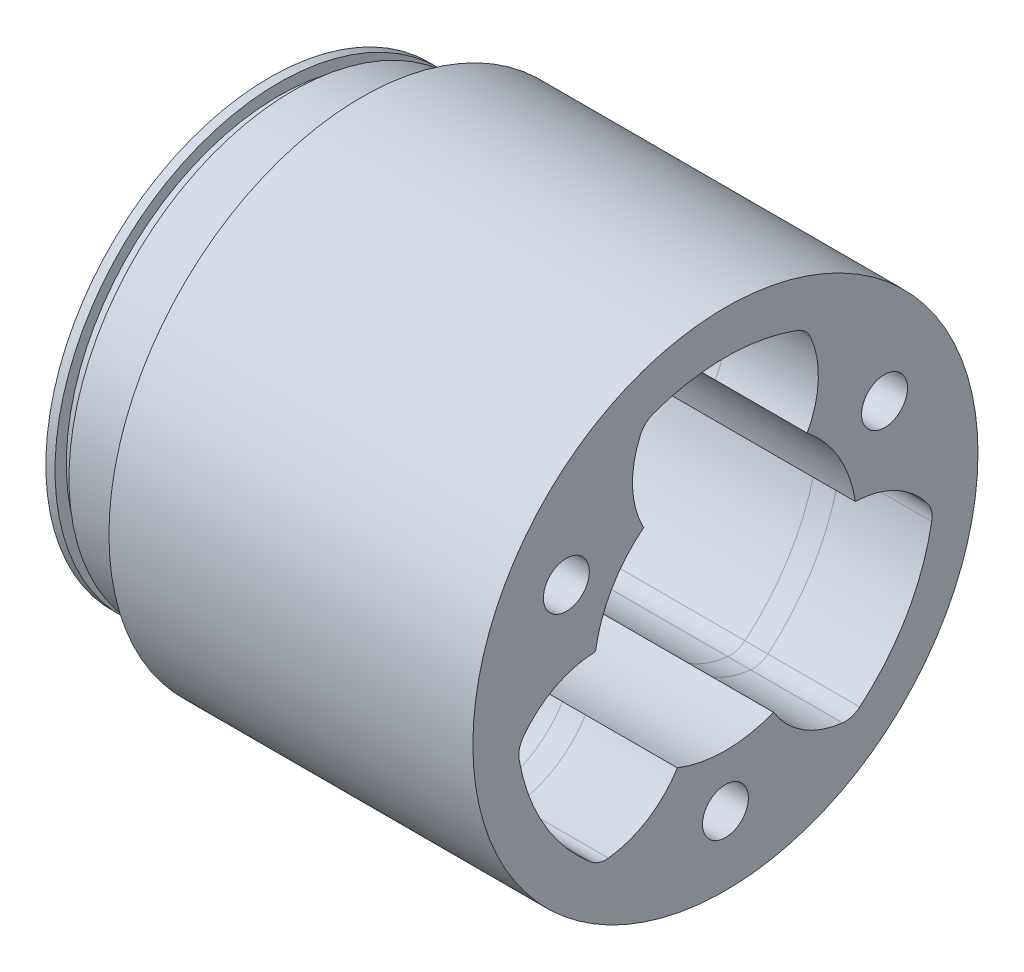
SolidWorks part; units mm, degrees
material "6061-T6 (SS)"
ref_plane "Front Plane" through (0, 0, 0) normal (0, 0, 1) x (1, 0, 0)
ref_plane "Top Plane" through (0, 0, 0) normal (0, 1, 0) x (1, 0, 0)
ref_plane "Right Plane" through (0, 0, 0) normal (1, 0, 0) x (0, 0, -1)
sketch "Sketch2" plane through (0, 0, 0) normal (0, 0, 1) x (1, 0, 0)
  line L0 (0, 0) -> (0, -30.9499)
  line L1 (0, -30.9499) -> (12.7, -30.9499)
  line L2 (12.7, -30.9499) -> (12.7, 0)
  line L3 (12.7, 0) -> (3.2004, 0)
  line L4 (11.9645, -30.9499) -> (0.5681, -30.9499) construction
  line L5 (3.2004, 0) -> (3.2004, -1.5621)
  line L6 (0, 0) -> (1.27, 0)
  line L7 (1.27, 0) -> (1.27, -1.5621)
  line L8 (1.27, -1.5621) -> (3.2004, -1.5621)
  dimension "D4" = 1.9304
  dimension "D5" = 0
  dimension "D6" = 58.7756
  dimension "D1" = 61.8998
  dimension "D2" = 12.7
  dimension "D3" = 1.27
revolve "Revolve1" add sketch "Sketch2" angle 360 about L4
sketch "Bolt Circle Pattern" plane through (12.7, 0, 0) normal (1, 0, 0) x (0, 0, -1)
  circle A3 centre (0, -30.9499) radius 4.1021
  circle A4 centre (0, -30.9499) radius 30.9499 construction
  circle A5 centre (0, -30.9499) radius 9.525 construction
  point P49 (9.525, -30.9499)
  point P51 (0, -40.4749)
  point P53 (-9.525, -30.9499)
  point P57 (0, -21.4249)
  dimension "D1" = 8.2042
  dimension "D2" = 19.05
sketch "Sketch4" plane through (12.7, 0, 0) normal (1, 0, 0) x (0, 0, -1)
  circle A0 centre (0, -30.9499) radius 34.925
  circle A1 centre (0, -30.9499) radius 30.9499 construction
  circle A2 centre (0, -30.9499) radius 18.161
  dimension "D1" = 69.85
  dimension "D2" = 36.322
extrude "Boss-Extrude1" add sketch "Sketch4" along normal blind 72.771
sketch "Sketch5" plane through (0, 0, 0) normal (1, 0, 0) x (0, 0, -1)
  line L0 (0, -10.6299) -> (-17.5976, -41.1099) construction
  line L1 (-17.5976, -41.1099) -> (17.5976, -41.1099) construction
  line L2 (17.5976, -41.1099) -> (0, -10.6299) construction
  line L3 (0, -10.6299) -> (0, -41.1099) construction
  line L4 (-17.5976, -41.1099) -> (8.7988, -25.8699) construction
  line L5 (17.5976, -41.1099) -> (-8.7988, -25.8699) construction
  arc A0 (-11.1418, -4.2233) -> (11.1418, -4.2233) centre (0, -10.6299) ccw
  arc A2 (-28.7168, -34.6641) -> (-17.575, -53.9623) centre (0, -30.9499) ccw
  arc A4 (-17.575, -53.9623) -> (-28.7168, -34.6641) centre (-17.5976, -41.1099) ccw
  arc A5 (28.7168, -34.6641) -> (17.575, -53.9623) centre (17.5976, -41.1099) ccw
  arc A6 (17.575, -53.9623) -> (28.7168, -34.6641) centre (0, -30.9499) ccw
  arc A7 (11.1418, -4.2233) -> (-11.1418, -4.2233) centre (0, -30.9499) ccw
  dimension "D2" = 12.8524
  dimension "D6" = 12.8524
  dimension "D5" = 12.8524
  dimension "D9" = 28.956
  dimension "D1" = 20.32
  dimension "D3" = 20.32
  dimension "D4" = 20.32
  dimension "D7" = 35.1953
  dimension "D8" = 35.1953
extrude "Cut-Extrude2" cut sketch "Sketch5" along normal up to next from offset 21.75
fillet "Tripod walls" radius 3.175 6 edges at (53.6105, -53.9623, 17.575) (53.6105, -53.9623, -17.575) (53.6105, -34.6641, 28.7168) (53.6105, -34.6641, -28.7168) (53.6105, -4.2233, 11.1418) (53.6105, -4.2233, -11.1418)
fillet "Tripod Face" [suppressed] radius 3.175
fillet "Bolt Hole Face" [suppressed] radius 3.175
ref_plane "Plane1" through (60.071, 0, 0) normal (1, 0, 0) x (0, 0, -1)
ref_plane "Plane2" through (66.421, 0, 0) normal (1, 0, 0) x (0, 0, -1)
split line "Split Line1" [suppressed]
sketch "Sketch12" plane through (85.471, 0, 0) normal (1, 0, 0) x (0, 0, -1)
  line L0 (-21.997, -18.2499) -> (21.997, -18.2499) construction
  line L1 (21.997, -18.2499) -> (0, -56.3499) construction
  line L2 (0, -56.3499) -> (-21.997, -18.2499) construction
  circle A0 centre (0, -30.9499) radius 25.4 construction
  circle A4 centre (-21.997, -18.2499) radius 3.175
  circle A9 centre (21.997, -18.2499) radius 3.175
  circle A12 centre (0, -56.3499) radius 3.175
  dimension "D2" = 6.35
extrude "Cut-Extrude3" cut sketch "Sketch12" against normal blind 63.5
sketch "Sketch13" plane through (85.471, 0, 0) normal (1, 0, 0) x (0, 0, -1)
  circle A1 centre (0, -30.9499) radius 34.925
  circle A2 centre (0, -30.9499) radius 34.925
  dimension "D1" = 0
extrude "Cut-Extrude4" cut sketch "Sketch13" against normal offset from surface (22.446 mm away) 41.275 up to face at (21.75, -42.5964, -20.1724)
fillet "Fillet6" [suppressed] radius 2.54
ref_plane "Plane5" through (24.925, 0, 0) normal (1, 0, 0) x (0, 0, -1)
split line "Split Line4"
sketch "Sketch14" [suppressed] plane through (63.025, 0, 0) normal (1, 0, 0) x (0, 0, -1)
  circle A0 centre (0, -30.5867) radius 18.161
  circle A1 centre (0, -30.5867) radius 18.161 construction
ref_plane "Plane3" through (47.15, 0, 0) normal (1, 0, 0) x (0, 0, -1)
split line "Split Line2"
ref_plane "Plane4" through (50.325, 0, 0) normal (1, 0, 0) x (0, 0, -1)
split line "Split Line3"
sketch "Sketch16" plane through (0, 0, 0) normal (-1, 0, 0) x (0, 0, 1)
  circle A0 centre (0, -30.9499) radius 22.86
  circle A1 centre (0, -30.9499) radius 30.9499 construction
  dimension "D1" = 45.72
extrude "Compensating Spacing" add sketch "Sketch16" along normal blind 1.016
hole_wizard "1/4 (0.2500) Dowel Hole1" positions "Bolt Circle Pattern" profile "Sketch15" hole size "1/4" standard "ANSI Inch" end condition through all
sketch "Sketch15" plane through (12.7, -21.4249, 0) normal (0, 1, 0) x (0, 0, -1)
  line L0 (0, 0) -> (0, 13.716)
  line L1 (0, 13.716) -> (3.175, 13.716)
  line L2 (3.175, 13.716) -> (3.175, 0)
  line L5 (3.175, 0) -> (0, 0)
  line L11 (0, -6.35) -> (0, 107.95) construction
  dimension "Thru Hole Dia." = 6.35
  dimension "Thru Hole Depth" = 13.716
extrude "5/16 Clearnce" cut sketch "Bolt Circle Pattern<2>" against normal up to surface (13.716 mm away) up to face at (-1.016, -30.9499, -12.7)
sketch "Bolt Circle Pattern<2>" plane through (12.7, 0, 0) normal (1, 0, 0) x (0, 0, -1) same geometry as "Bolt Circle Pattern"
equation "\"D9@Sketch5\"=2.28/2"
equation "\"D8@Sketch5\"=\"D7@Sketch5\""
equation "\"Drill_Hole\"=0.25"
equation "\"D2@Sketch12\"=\"Drill_Hole\""
